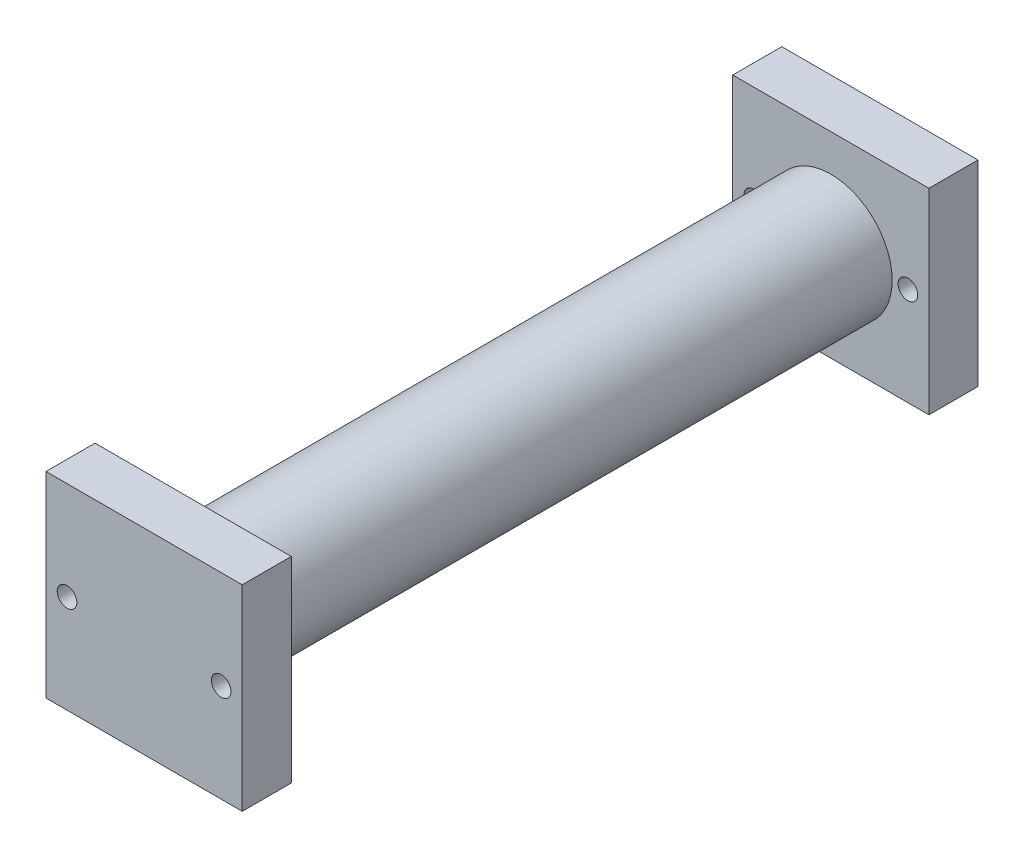
SolidWorks part; units mm, degrees
ref_plane "前基準面" through (0, 0, 0) normal (0, 0, 1) x (1, 0, 0)
ref_plane "上基準面" through (0, 0, 0) normal (0, 1, 0) x (1, 0, 0)
ref_plane "右基準面" through (0, 0, 0) normal (1, 0, 0) x (0, 0, -1)
sketch "草圖1" plane through (0, 0, 0) normal (0, 0, 1) x (1, 0, 0)
  line L1 (-20, 20) -> (20, 20)
  line L2 (-20, 20) -> (-20, -20)
  line L3 (-20, -20) -> (20, -20)
  line L4 (20, 20) -> (20, -20)
  line L5 (-20, 20) -> (20, -20) construction
  line L6 (-20, -20) -> (20, 20) construction
  point P0 (0, 0)
extrude "填料-伸長1" add sketch "草圖1" along normal blind 10
sketch "草圖2" plane through (0, 0, 10) normal (0, 0, 1) x (1, 0, 0)
  circle A0 centre (0, 0) radius 12.5
extrude "填料-伸長2" add sketch "草圖2" along normal blind 130
sketch "草圖3" plane through (0, 0, 140) normal (0, 0, 1) x (1, 0, 0)
  line L1 (-20, 20) -> (20, 20)
  line L2 (-20, 20) -> (-20, -20)
  line L3 (-20, -20) -> (20, -20)
  line L4 (20, 20) -> (20, -20)
  line L5 (-20, 20) -> (20, -20) construction
  line L6 (-20, -20) -> (20, 20) construction
  point P0 (0, 0)
extrude "填料-伸長3" add sketch "草圖3" along normal blind 10
sketch "草圖4" plane through (0, 0, 150) normal (0, 0, 1) x (1, 0, 0)
  line L0 (15.714, 0) -> (-15.714, 0)
  circle A0 centre (-15.714, 0) radius 2
  circle A1 centre (15.714, 0) radius 2
  point P4 (0, 0)
extrude "除料-伸長1" cut sketch "草圖4" against normal blind 10 contours A0 region at (-17.6574, 0, 150)
sketch "草圖5" plane through (0, 0, 150) normal (0, 0, 1) x (1, 0, 0)
  line L0 (0, 0) -> (15.71, 0)
  circle A0 centre (15.71, 0) radius 2
extrude "除料-伸長2" cut sketch "草圖5" against normal blind 10 contours A0 region at (15.71, -1.9434, 150)
sketch "草圖6" plane through (0, 0, 0) normal (0, 0, -1) x (-1, 0, 0)
  line L0 (0, 0) -> (-15.71, 0)
  circle A0 centre (-15.71, 0) radius 2
  point P4 (0, 0)
extrude "除料-伸長3" cut sketch "草圖6" against normal blind 10 contours A0 region at (17.6534, 0, 0)
sketch "草圖7" plane through (0, 0, 0) normal (0, 0, -1) x (-1, 0, 0)
  line L0 (0, 0) -> (15.71, 0)
  circle A0 centre (15.71, 0) radius 2
extrude "除料-伸長4" cut sketch "草圖7" against normal blind 10 contours A0 region at (-15.71, -1.9434, 0)
